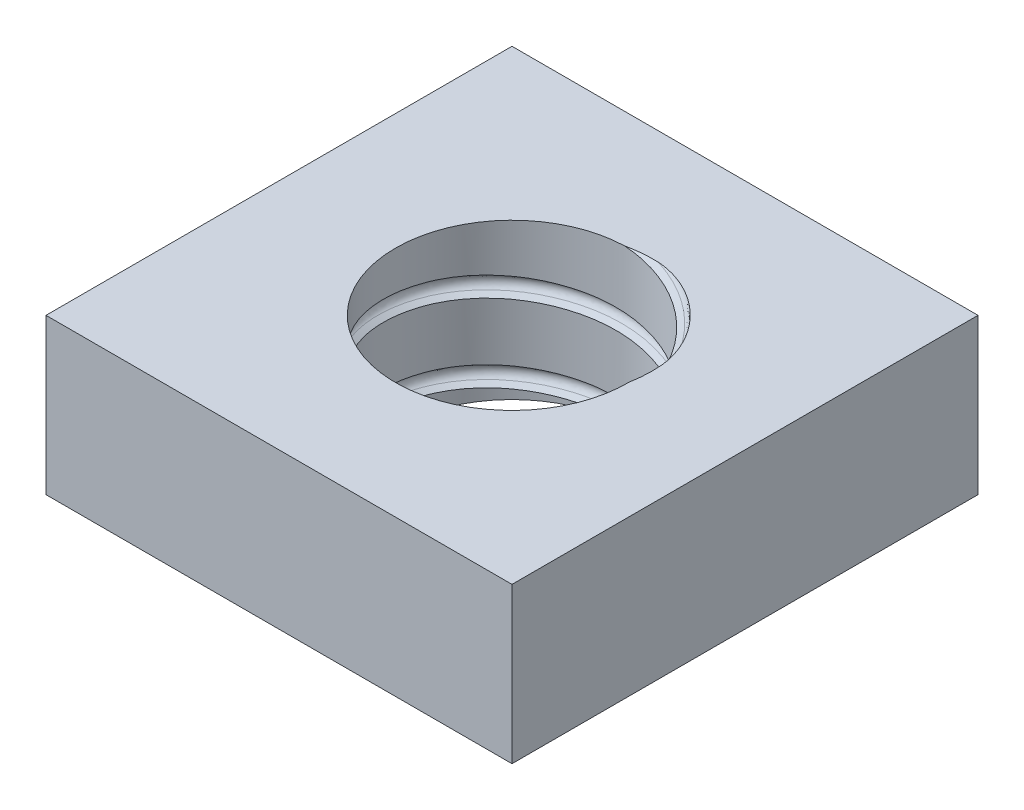
SolidWorks part; units mm, degrees
ref_plane "Alzado" through (0, 0, 0) normal (0, 0, 1) x (1, 0, 0)
ref_plane "Planta" through (0, 0, 0) normal (0, 1, 0) x (1, 0, 0)
ref_plane "Vista lateral" through (0, 0, 0) normal (1, 0, 0) x (0, 0, -1)
sketch "Croquis1" plane through (0, 0, 0) normal (0, 1, 0) x (1, 0, 0)
  line L1 (-3, -3) -> (3, -3)
  line L2 (-3, -3) -> (-3, 3)
  line L3 (-3, 3) -> (3, 3)
  line L4 (3, -3) -> (3, 3)
  line L5 (-3, -3) -> (3, 3) construction
  line L6 (-3, 3) -> (3, -3) construction
  circle A0 centre (0, 0) radius 1.5
  point P0 (0, 0)
  dimension "D1" = 3
  dimension "D2" = 6
  dimension "D3" = 6
extrude "Extruir1" add sketch "Croquis1" along normal blind 2
sketch "Croquis2" plane through (0, 2, 0) normal (0, 1, 0) x (1, 0, 0)
  circle A0 centre (0, 0) radius 1.5
sketch "Croquis3" plane through (0, 0, 0) normal (0, 0, 1) x (1, 0, 0)
  line L0 (1.5228, 0.8716) -> (0.9165, 0.8716) construction
  line L2 (1.1165, 1.2793) -> (1.1165, 1.2716)
  line L3 (1.1165, 1.2716) -> (0.9165, 1.2716)
  line L4 (0.9165, 1.2716) -> (0.9165, 0.4716)
  line L5 (1.5728, 0.9582) -> (1.1665, 1.1927)
  line L7 (1.1665, 0.5505) -> (1.5728, 0.785)
  line L8 (0.9165, 0.4716) -> (1.1165, 0.4716)
  line L9 (1.1165, 0.4716) -> (1.1165, 0.4639)
  line L11 (0.7916, 0.2428) -> (0.7916, -0.1072) [skipped]
  arc A0 (1.5728, 0.785) -> (1.5728, 0.9582) centre (1.5228, 0.8716) ccw
  arc A1 (1.1665, 1.1927) -> (1.1165, 1.2793) centre (1.2165, 1.2793) cw
  arc A2 (1.1165, 0.4639) -> (1.1665, 0.5505) centre (1.2165, 0.4639) cw
  point P9 (1.1165, 1.2216)
  point P14 (1.1165, 0.5216)
  dimension "D2" = 0.8
  dimension "D4" = 0.2
  dimension "D1" = 0.1
  dimension "D3" = 0.7
ref_plane "Plano1" through (0, 0.5, 0) normal (0, 1, 0) x (-1, 0, 0)
sketch "Croquis4" plane through (0, 0.5, 0) normal (0, 1, 0) x (-1, 0, 0)
  circle A0 centre (0, 0) radius 1.4
  dimension "D1" = 2.8
sketch "Croquis5" plane through (0, 0, 0) normal (0, -1, 0) x (1, 0, 0)
  circle A0 centre (0, 0) radius 1.5
  dimension "D1" = 3
extrude "Extruir2" [suppressed] cut sketch "Croquis5" against normal blind 0.1
sketch "Croquis6" plane through (0, 0, 0) normal (0, -1, 0) x (1, 0, 0)
  circle A0 centre (0, 0) radius 1.5
curve "Hélice/Espiral3" pitch 1 height 8 radius 1.5 centre (0, 0, 0) axis (0, 1, 0) start towards (0.7071, 0, -0.7071)
sweep "Cortar-Barrer11" cut profiles "Croquis3" path "Hélice/Espiral3"
